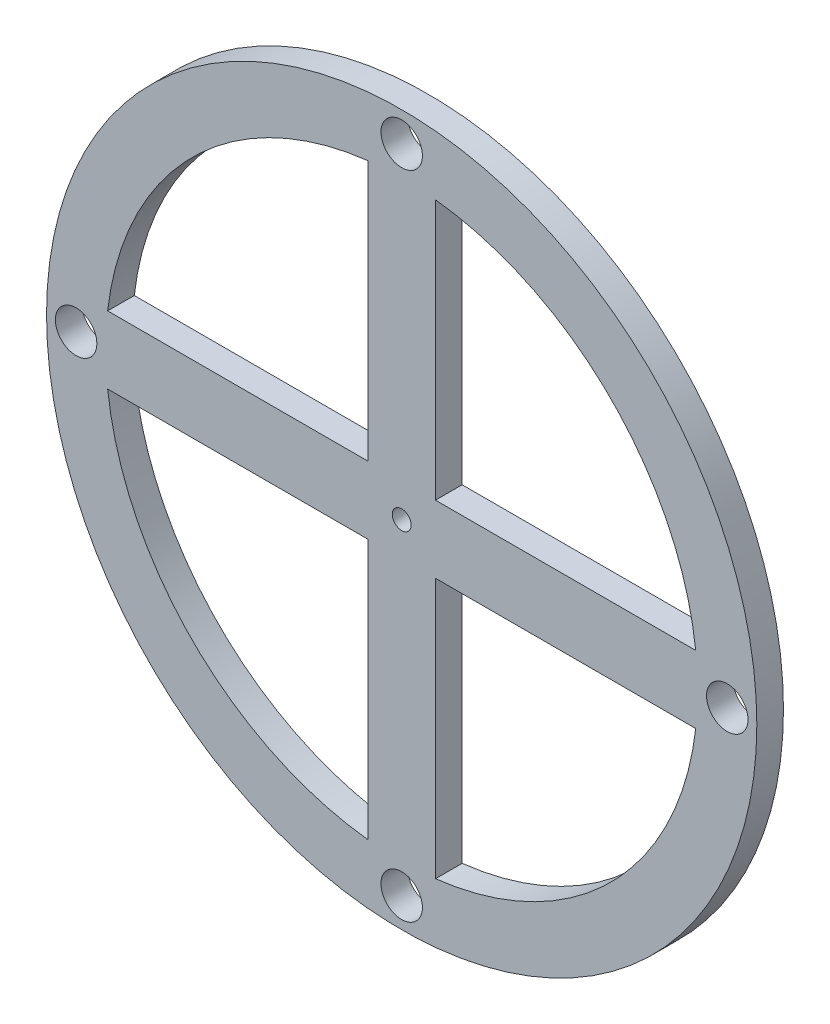
SolidWorks part; units mm, degrees
ref_plane "Plan de face" through (0, 0, 0) normal (0, 0, 1) x (1, 0, 0)
ref_plane "Plan de dessus" through (0, 0, 0) normal (0, 1, 0) x (1, 0, 0)
ref_plane "Plan de droite" through (0, 0, 0) normal (1, 0, 0) x (0, 0, -1)
sketch "Esquisse1" plane through (0, 0, 0) normal (0, 0, 1) x (1, 0, 0)
  line L0 (50, 0) -> (60, 0) construction
  line L2 (5.7143, 49.6724) -> (5.7143, 5.7143)
  line L4 (-5.7143, 49.6724) -> (-5.7143, 5.7143)
  line L5 (0, 0) -> (0, 12.222) construction
  line L6 (0, -50) -> (0, -60) construction
  line L7 (-49.6724, 5.7143) -> (-5.7143, 5.7143)
  line L9 (-49.6724, -5.7143) -> (-5.7143, -5.7143)
  line L11 (0, 0) -> (12.4869, 0) construction
  line L13 (5.7143, 5.7143) -> (49.6724, 5.7143)
  line L14 (5.7143, -5.7143) -> (49.6724, -5.7143)
  line L16 (-5.7143, -5.7143) -> (-5.7143, -49.6724)
  line L18 (5.7143, -5.7143) -> (5.7143, -49.6724)
  circle A0 centre (0, 0) radius 60
  circle A1 centre (0, 0) radius 50
  circle A2 centre (0, 0) radius 1.595
  circle A11 centre (0, -55) radius 3.5
  circle A12 centre (55, 0) radius 3.5
  circle A13 centre (-55, 0) radius 3.5
  circle A14 centre (0, 55) radius 3.5
  dimension "D1" = 120
  dimension "D2" = 100
  dimension "D3" = 3.19
  dimension "D4" = 7
  dimension "D5" = 7
extrude "Boss.-Extru.4" add sketch "Esquisse1" along normal blind 4.5 contours A0 A13 A12 A11 A1 A14 | L2 A1 L4 L7 L9 L16 L18 L14 L13 A2 region at (4.3001, 27.6933, 0) region at (-59.8303, 0, 0)
